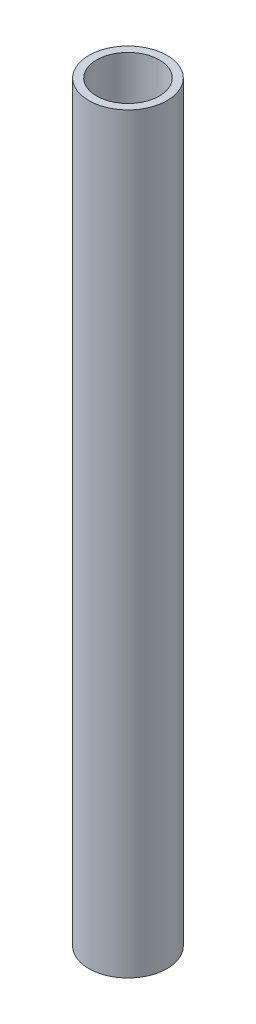
SolidWorks part; units mm, degrees
material "Custom Plastic"
ref_plane "X-Y Datum" through (0, 0, 0) normal (0, 0, 1) x (1, 0, 0)
ref_plane "X-Z Datum" through (0, 0, 0) normal (0, 1, 0) x (1, 0, 0)
ref_plane "Y-Z Datum" through (0, 0, 0) normal (1, 0, 0) x (0, 0, -1)
ref_point "Middle point"
sketch "Sketch2" plane through (0, 0, 0) normal (0, 1, 0) x (1, 0, 0)
  circle A0 centre (0, 0) radius 12.7
  circle A1 centre (0, 0) radius 15.875
  dimension "D1" = 31.75
extrude "Tube Stock - Extrude" add sketch "Sketch2" along normal blind 152.4 and the other way blind 152.4
equation "\"Torsion Tube Stock Outer Diameter\"= 1.25"
equation "\"Torsion Tube Stock Wall Thickness\"= 0.25"
equation "\"D1@Sketch2\"= \"Torsion Tube Stock Outer Diameter\""
equation "\"D2@Sketch2\"= \"Torsion Tube Stock Outer Diameter\" - \"Torsion Tube Stock Wall Thickness\""
equation "\"Torsion Tube Stock Length\"= 12in"
equation "\"D1@Tube Stock - Extrude\"=\"Torsion Tube Stock Length\"/2"
equation "\"D2@Tube Stock - Extrude\"=\"Torsion Tube Stock Length\"/2"
